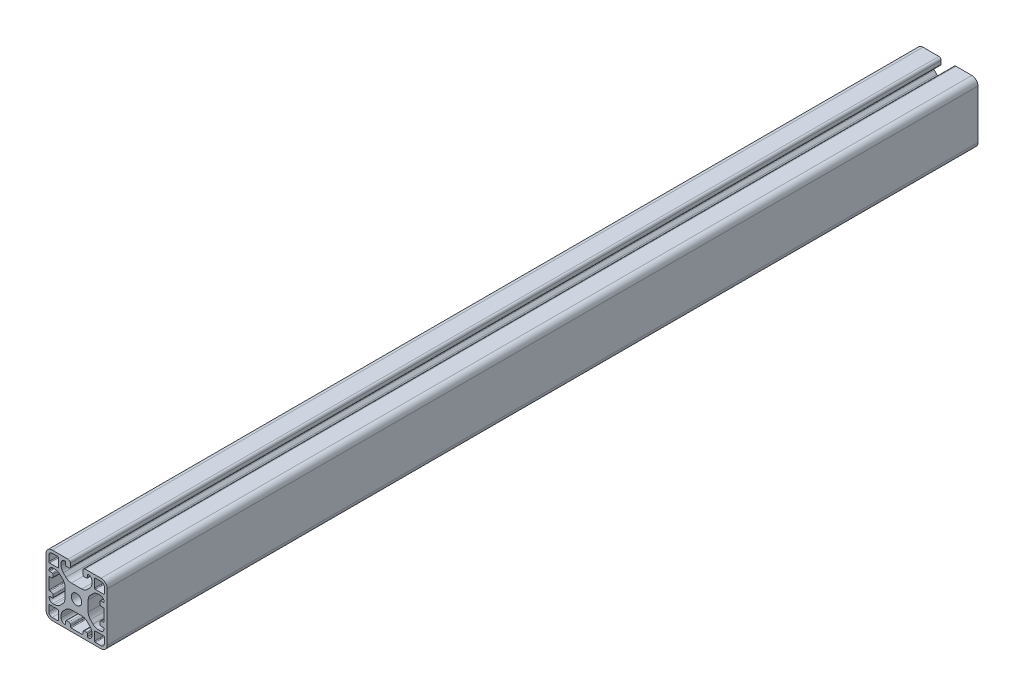
SolidWorks part; units mm, degrees
ref_plane "Ebene vorne" through (0, 0, 0) normal (0, 0, 1) x (1, 0, 0)
ref_plane "Ebene oben" through (0, 0, 0) normal (0, 1, 0) x (1, 0, 0)
ref_plane "Ebene rechts" through (0, 0, 0) normal (1, 0, 0) x (0, 0, -1)
ref_plane "Ebene1" through (0, 0, 570) normal (0, 0, 1) x (1, 0, 0)
sketch "Skizze1" plane through (0, 0, 570) normal (0, 0, 1) x (1, 0, 0)
  line L0 (0, 38.2) -> (3.7, 38.2)
  line L1 (4.2, 37.7) -> (4.2, 32.3)
  line L2 (3.7, 31.8) -> (-1.7, 31.8)
  line L3 (-2.2, 32.3) -> (-2.2, 36)
  line L4 (-2.2, 4) -> (-2.2, 7.7)
  line L5 (-1.7, 8.2) -> (3.7, 8.2)
  line L6 (4.2, 7.7) -> (4.2, 2.3)
  line L7 (3.7, 1.8) -> (0, 1.8)
  line L8 (32, 1.8) -> (28.3, 1.8)
  line L9 (27.8, 2.3) -> (27.8, 7.7)
  line L10 (28.3, 8.2) -> (33.7, 8.2)
  line L11 (34.2, 7.7) -> (34.2, 4)
  line L12 (34.2, 36) -> (34.2, 32.3)
  line L13 (33.7, 31.8) -> (28.3, 31.8)
  line L14 (27.8, 32.3) -> (27.8, 37.7)
  line L15 (28.3, 38.2) -> (32, 38.2)
  line L16 (12.5924, 12.4) -> (19.4076, 12.4)
  line L17 (22.9431, 10.9355) -> (24.6355, 9.2431)
  line L18 (26.1, 5.7076) -> (26.1, 4.5)
  line L19 (23.1, 2.5) -> (23.1, 4.15)
  line L20 (22.6, 4.65) -> (21.1, 4.65)
  line L21 (20.1, 3.65) -> (20.1, 2.5)
  line L22 (19.6, 2) -> (12.4, 2)
  line L23 (11.9, 2.5) -> (11.9, 3.65)
  line L24 (10.9, 4.65) -> (9.4, 4.65)
  line L25 (8.9, 4.15) -> (8.9, 2.5)
  line L26 (5.9, 4.5) -> (5.9, 5.7076)
  line L27 (7.3645, 9.2431) -> (9.0569, 10.9355)
  line L28 (-0.35, 15.9) -> (-1.5, 15.9)
  line L29 (-2, 16.4) -> (-2, 23.6)
  line L30 (-1.5, 24.1) -> (-0.35, 24.1)
  line L31 (0.65, 25.1) -> (0.65, 26.6)
  line L32 (0.15, 27.1) -> (-1.5, 27.1)
  line L33 (0.5, 30.1) -> (1.7076, 30.1)
  line L34 (5.2431, 28.6355) -> (6.9355, 26.9431)
  line L35 (8.4, 23.4076) -> (8.4, 16.5924)
  line L36 (6.9355, 13.0569) -> (5.2431, 11.3645)
  line L37 (1.7076, 9.9) -> (0.5, 9.9)
  line L38 (-1.5, 12.9) -> (0.15, 12.9)
  line L39 (0.65, 13.4) -> (0.65, 14.9)
  line L40 (23.6, 16.5924) -> (23.6, 23.4076)
  line L41 (25.0645, 26.9431) -> (26.7569, 28.6355)
  line L42 (30.2924, 30.1) -> (31.5, 30.1)
  line L43 (33.5, 27.1) -> (31.85, 27.1)
  line L44 (31.35, 26.6) -> (31.35, 25.1)
  line L45 (32.35, 24.1) -> (33.5, 24.1)
  line L46 (34, 23.6) -> (34, 16.4)
  line L47 (33.5, 15.9) -> (32.35, 15.9)
  line L48 (31.35, 14.9) -> (31.35, 13.4)
  line L49 (31.85, 12.9) -> (33.5, 12.9)
  line L50 (31.5, 9.9) -> (30.2924, 9.9)
  line L51 (26.7569, 11.3645) -> (25.0645, 13.0569)
  line L52 (23.1, 35.85) -> (23.1, 37.5)
  line L53 (26.1, 35.5) -> (26.1, 34.2924)
  line L54 (24.6355, 30.7569) -> (22.9431, 29.0645)
  line L55 (19.4076, 27.6) -> (12.5924, 27.6)
  line L56 (9.0569, 29.0645) -> (7.3645, 30.7569)
  line L57 (5.9, 34.2924) -> (5.9, 35.5)
  line L58 (8.9, 37.5) -> (8.9, 35.85)
  line L59 (9.4, 35.35) -> (10.9, 35.35)
  line L60 (11.9, 36.35) -> (11.9, 38.5)
  line L61 (10.4, 40) -> (0, 40)
  line L62 (-4, 36) -> (-4, 4)
  line L63 (0, 0) -> (32, 0)
  line L64 (36, 4) -> (36, 36)
  line L65 (32, 40) -> (21.6, 40)
  line L66 (20.1, 38.5) -> (20.1, 36.35)
  line L67 (21.1, 35.35) -> (22.6, 35.35)
  circle A0 centre (16, 20) radius 3.4
  arc A1 (3.7, 38.2) -> (4.2, 37.7) centre (3.7, 37.7) cw
  arc A2 (4.2, 32.3) -> (3.7, 31.8) centre (3.7, 32.3) cw
  arc A3 (-1.7, 31.8) -> (-2.2, 32.3) centre (-1.7, 32.3) cw
  arc A4 (-2.2, 36) -> (0, 38.2) centre (0, 36) cw
  arc A5 (-2.2, 7.7) -> (-1.7, 8.2) centre (-1.7, 7.7) cw
  arc A6 (3.7, 8.2) -> (4.2, 7.7) centre (3.7, 7.7) cw
  arc A7 (4.2, 2.3) -> (3.7, 1.8) centre (3.7, 2.3) cw
  arc A8 (0, 1.8) -> (-2.2, 4) centre (0, 4) cw
  arc A9 (28.3, 1.8) -> (27.8, 2.3) centre (28.3, 2.3) cw
  arc A10 (27.8, 7.7) -> (28.3, 8.2) centre (28.3, 7.7) cw
  arc A11 (33.7, 8.2) -> (34.2, 7.7) centre (33.7, 7.7) cw
  arc A12 (34.2, 4) -> (32, 1.8) centre (32, 4) cw
  arc A13 (34.2, 32.3) -> (33.7, 31.8) centre (33.7, 32.3) cw
  arc A14 (28.3, 31.8) -> (27.8, 32.3) centre (28.3, 32.3) cw
  arc A15 (27.8, 37.7) -> (28.3, 38.2) centre (28.3, 37.7) cw
  arc A16 (32, 38.2) -> (34.2, 36) centre (32, 36) cw
  arc A17 (19.4076, 12.4) -> (22.9431, 10.9355) centre (19.4076, 7.4) cw
  arc A18 (24.6355, 9.2431) -> (26.1, 5.7076) centre (21.1, 5.7076) cw
  arc A19 (26.1, 4.5) -> (23.6, 2) centre (23.6, 4.5) cw
  arc A20 (23.6, 2) -> (23.1, 2.5) centre (23.6, 2.5) cw
  arc A21 (23.1, 4.15) -> (22.6, 4.65) centre (22.6, 4.15) ccw
  arc A22 (21.1, 4.65) -> (20.1, 3.65) centre (21.1, 3.65) ccw
  arc A23 (20.1, 2.5) -> (19.6, 2) centre (19.6, 2.5) cw
  arc A24 (12.4, 2) -> (11.9, 2.5) centre (12.4, 2.5) cw
  arc A25 (11.9, 3.65) -> (10.9, 4.65) centre (10.9, 3.65) ccw
  arc A26 (9.4, 4.65) -> (8.9, 4.15) centre (9.4, 4.15) ccw
  arc A27 (8.9, 2.5) -> (8.4, 2) centre (8.4, 2.5) cw
  arc A28 (8.4, 2) -> (5.9, 4.5) centre (8.4, 4.5) cw
  arc A29 (5.9, 5.7076) -> (7.3645, 9.2431) centre (10.9, 5.7076) cw
  arc A30 (9.0569, 10.9355) -> (12.5924, 12.4) centre (12.5924, 7.4) cw
  arc A31 (-1.5, 15.9) -> (-2, 16.4) centre (-1.5, 16.4) cw
  arc A32 (-2, 23.6) -> (-1.5, 24.1) centre (-1.5, 23.6) cw
  arc A33 (-0.35, 24.1) -> (0.65, 25.1) centre (-0.35, 25.1) ccw
  arc A34 (0.65, 26.6) -> (0.15, 27.1) centre (0.15, 26.6) ccw
  arc A35 (-1.5, 27.1) -> (-2, 27.6) centre (-1.5, 27.6) cw
  arc A36 (-2, 27.6) -> (0.5, 30.1) centre (0.5, 27.6) cw
  arc A37 (1.7076, 30.1) -> (5.2431, 28.6355) centre (1.7076, 25.1) cw
  arc A38 (6.9355, 26.9431) -> (8.4, 23.4076) centre (3.4, 23.4076) cw
  arc A39 (8.4, 16.5924) -> (6.9355, 13.0569) centre (3.4, 16.5924) cw
  arc A40 (5.2431, 11.3645) -> (1.7076, 9.9) centre (1.7076, 14.9) cw
  arc A41 (0.5, 9.9) -> (-2, 12.4) centre (0.5, 12.4) cw
  arc A42 (-2, 12.4) -> (-1.5, 12.9) centre (-1.5, 12.4) cw
  arc A43 (0.15, 12.9) -> (0.65, 13.4) centre (0.15, 13.4) ccw
  arc A44 (0.65, 14.9) -> (-0.35, 15.9) centre (-0.35, 14.9) ccw
  arc A45 (23.6, 23.4076) -> (25.0645, 26.9431) centre (28.6, 23.4076) cw
  arc A46 (26.7569, 28.6355) -> (30.2924, 30.1) centre (30.2924, 25.1) cw
  arc A47 (31.5, 30.1) -> (34, 27.6) centre (31.5, 27.6) cw
  arc A48 (34, 27.6) -> (33.5, 27.1) centre (33.5, 27.6) cw
  arc A49 (31.85, 27.1) -> (31.35, 26.6) centre (31.85, 26.6) ccw
  arc A50 (31.35, 25.1) -> (32.35, 24.1) centre (32.35, 25.1) ccw
  arc A51 (33.5, 24.1) -> (34, 23.6) centre (33.5, 23.6) cw
  arc A52 (34, 16.4) -> (33.5, 15.9) centre (33.5, 16.4) cw
  arc A53 (32.35, 15.9) -> (31.35, 14.9) centre (32.35, 14.9) ccw
  arc A54 (31.35, 13.4) -> (31.85, 12.9) centre (31.85, 13.4) ccw
  arc A55 (33.5, 12.9) -> (34, 12.4) centre (33.5, 12.4) cw
  arc A56 (34, 12.4) -> (31.5, 9.9) centre (31.5, 12.4) cw
  arc A57 (30.2924, 9.9) -> (26.7569, 11.3645) centre (30.2924, 14.9) cw
  arc A58 (25.0645, 13.0569) -> (23.6, 16.5924) centre (28.6, 16.5924) cw
  arc A59 (22.6, 35.35) -> (23.1, 35.85) centre (22.6, 35.85) ccw
  arc A60 (23.1, 37.5) -> (23.6, 38) centre (23.6, 37.5) cw
  arc A61 (23.6, 38) -> (26.1, 35.5) centre (23.6, 35.5) cw
  arc A62 (26.1, 34.2924) -> (24.6355, 30.7569) centre (21.1, 34.2924) cw
  arc A63 (22.9431, 29.0645) -> (19.4076, 27.6) centre (19.4076, 32.6) cw
  arc A64 (12.5924, 27.6) -> (9.0569, 29.0645) centre (12.5924, 32.6) cw
  arc A65 (7.3645, 30.7569) -> (5.9, 34.2924) centre (10.9, 34.2924) cw
  arc A66 (5.9, 35.5) -> (8.4, 38) centre (8.4, 35.5) cw
  arc A67 (8.4, 38) -> (8.9, 37.5) centre (8.4, 37.5) cw
  arc A68 (8.9, 35.85) -> (9.4, 35.35) centre (9.4, 35.85) ccw
  arc A69 (10.9, 35.35) -> (11.9, 36.35) centre (10.9, 36.35) ccw
  arc A70 (11.9, 38.5) -> (10.4, 40) centre (10.4, 38.5) ccw
  arc A71 (0, 40) -> (-4, 36) centre (0, 36) ccw
  arc A72 (-4, 4) -> (0, 0) centre (0, 4) ccw
  arc A73 (32, 0) -> (36, 4) centre (32, 4) ccw
  arc A74 (36, 36) -> (32, 40) centre (32, 36) ccw
  arc A75 (21.6, 40) -> (20.1, 38.5) centre (21.6, 38.5) ccw
  arc A76 (20.1, 36.35) -> (21.1, 35.35) centre (21.1, 36.35) ccw
extrude "Aufsatz-Linear austragen1" add sketch "Skizze1" against normal blind 570
